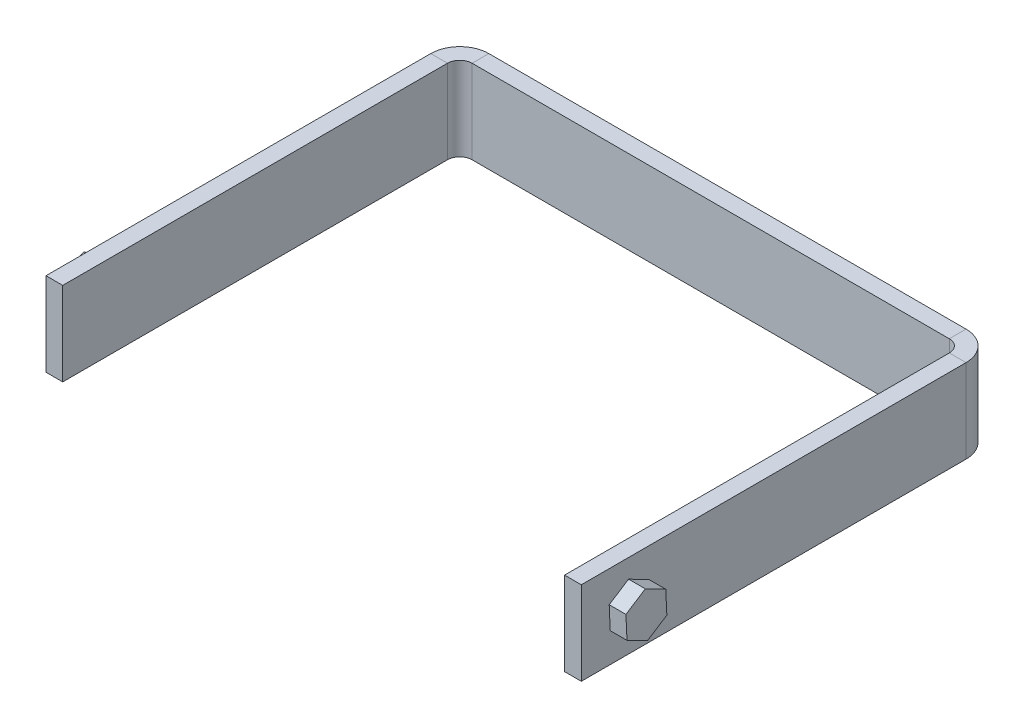
SolidWorks part; units mm, degrees
note: The reader was unsure of these and kept them because the rebuilt part matched: flange length of "Edge-Flange1".
ref_plane "Front Plane" through (0, 0, 0) normal (0, 0, 1) x (1, 0, 0)
ref_plane "Top Plane" through (0, 0, 0) normal (0, 1, 0) x (1, 0, 0)
ref_plane "Right Plane" through (0, 0, 0) normal (1, 0, 0) x (0, 0, -1)
sketch "Sketch1" plane through (0, 0, 0) normal (0, 0, 1) x (1, 0, 0)
  line L1 (-16, 2.5) -> (16, 2.5)
  line L2 (-16, 2.5) -> (-16, -2.5)
  line L3 (-16, -2.5) -> (16, -2.5)
  line L4 (16, 2.5) -> (16, -2.5)
  line L5 (-16, 2.5) -> (16, -2.5) construction
  line L6 (-16, -2.5) -> (16, 2.5) construction
  point P0 (0, 0)
  dimension "D1" = 32
  dimension "D2" = 5
base flange "Base-Flange1" sketch "Sketch1" thickness 1 reverse thickness direction no parameters "D1"=0.7366
edge flange "Edge-Flange1" sketch "Sketch10" flange profiles "Sketch10", "Sketch11" flange angle 90 flange length 24.7366 bend radius 0.7366 thickness 1 relief rectangular parameters "D6"=10, "D8"=0.2
sketch "Sketch10" plane through (-16, 0, 0) normal (-1, 0, 0) x (0, -1, 0)
  line L0 (-2.5, 0) -> (2.5, 0) construction
  line L1 (-2.5, 0) -> (2.5, 0)
  line L2 (-2.5, 0) -> (-2.5, 23.7366)
  line L3 (-2.5, 23.7366) -> (2.5, 23.7366)
  line L4 (2.5, 23.7366) -> (2.5, 0)
sketch "Sketch11" plane through (16, 0, 0) normal (1, 0, 0) x (0, 1, 0)
  line L0 (-2.5, 0) -> (2.5, 0) construction
  line L1 (-2.5, 0) -> (2.5, 0)
  line L2 (-2.5, 0) -> (-2.5, 23.7366)
  line L3 (-2.5, 23.7366) -> (2.5, 23.7366)
  line L4 (2.5, 23.7366) -> (2.5, 0)
bend "EdgeBend1" bend radius 0.7366 bend angle 90 parameters "D5"=1
bend "EdgeBend2" bend radius 0.7366 bend angle 90 parameters "D5"=2
sketch "Sketch12" plane through (16, 0, 0) normal (1, 0, 0) x (0, 0, -1)
  line L1 (-19.6229, -0.6329) -> (-19.6864, 0.7428)
  line L2 (-19.6864, 0.7428) -> (-20.9095, 1.3757)
  line L3 (-20.9095, 1.3757) -> (-22.0691, 0.6329)
  line L4 (-22.0691, 0.6329) -> (-22.0057, -0.7428)
  line L5 (-22.0057, -0.7428) -> (-20.7826, -1.3757)
  line L6 (-20.7826, -1.3757) -> (-19.6229, -0.6329)
  circle A0 centre (-20.846, 0) radius 1.1926 construction
extrude "Boss-Extrude1" add sketch "Sketch12" along normal blind 1
sketch "Sketch13" plane through (-16, 0, 0) normal (-1, 0, 0) x (0, 0, 1)
  line L1 (22.1414, -0.6499) -> (21.9623, 0.9602)
  line L2 (21.9623, 0.9602) -> (20.4784, 1.61)
  line L3 (20.4784, 1.61) -> (19.1736, 0.6499)
  line L4 (19.1736, 0.6499) -> (19.3528, -0.9602)
  line L5 (19.3528, -0.9602) -> (20.8367, -1.61)
  line L6 (20.8367, -1.61) -> (22.1414, -0.6499)
  circle A0 centre (20.6575, 0) radius 1.4029 construction
extrude "Boss-Extrude2" add sketch "Sketch13" along normal blind 1
sketch "Bend-Lines1" [suppressed] plane through (0, 0, 0) normal (0, 1, 0) x (1, 0, 0)
sketch "Bounding-Box1" [suppressed] plane through (0, 0, 0) normal (0, 1, 0) x (1, 0, 0)
sheet metal parameters "Sheet-Metal1" thickness 1 parameters "D1"=0.7366
flat pattern "Flat-Pattern1" [suppressed]
sketch "Bend-Lines2" plane through (0, 0, 0) normal (0, 1, 0) x (1, 0, 0)
sketch3d "Bounding-Box2" [suppressed]
  line L0 (12.5, -2.5, 0) -> (-12.5, -2.5, 0) construction
  line L1 (12.5, 2.5, 0) -> (-12.5, 2.5, 0) construction
  line L2 (12.5, -2.5, 0) -> (12.5, 2.5, 0) construction
  line L3 (-12.5, -2.5, 0) -> (-12.5, 2.5, 0) construction
sheet metal parameters "Sheet-Metal2" thickness 1 parameters "D1"=0.7366
flat pattern "Flat-Pattern1"
sketch "Bend-Lines2" plane through (0, 0, 0) normal (0, 0, 1) x (1, 0, 0)
  line L0 (15.2346, -2.5) -> (15.2346, 2.5) construction
  line L1 (-15.2346, 2.5) -> (-15.2346, -2.5) construction
  line L2 (15.2346, -2.5) -> (15.2346, 2.5) construction
  line L3 (-15.2346, 2.5) -> (-15.2346, -2.5) construction
sketch3d "Bounding-Box2" [suppressed]
  line L0 (-39.2058, -2.5, 0) -> (39.2058, -2.5, 0) construction
  line L1 (-39.2058, 2.5, 0) -> (39.2058, 2.5, 0) construction
  line L2 (-39.2058, -2.5, 0) -> (-39.2058, 2.5, 0) construction
  line L3 (39.2058, -2.5, 0) -> (39.2058, 2.5, 0) construction
bend of the flat pattern "Flatten-<EdgeBend1>1"
bend of the flat pattern "Flatten-<EdgeBend2>1"
sheet metal parameters "Sheet-Metal3" thickness 1 parameters "D1"=0.7366
flat pattern "Flat-Pattern1"
sketch "Bend-Lines2" plane through (0, 0, 0) normal (0, 0, 1) x (1, 0, 0)
  line L0 (15.2346, -2.5) -> (15.2346, 2.5) construction
  line L1 (-15.2346, 2.5) -> (-15.2346, -2.5) construction
  line L2 (15.2346, -2.5) -> (15.2346, 2.5) construction
  line L3 (-15.2346, 2.5) -> (-15.2346, -2.5) construction
sketch3d "Bounding-Box2" [suppressed]
  line L0 (-39.2058, -2.5, 0) -> (39.2058, -2.5, 0) construction
  line L1 (-39.2058, 2.5, 0) -> (39.2058, 2.5, 0) construction
  line L2 (-39.2058, -2.5, 0) -> (-39.2058, 2.5, 0) construction
  line L3 (39.2058, -2.5, 0) -> (39.2058, 2.5, 0) construction
bend of the flat pattern "Flatten-<EdgeBend1>1"
bend of the flat pattern "Flatten-<EdgeBend2>1"
sheet metal parameters "Sheet-Metal4" thickness 1 parameters "D1"=0.7366
flat pattern "Flat-Pattern1"
sketch "Bend-Lines2" plane through (0, 0, 0) normal (0, 0, 1) x (1, 0, 0)
  line L0 (15.2346, -2.5) -> (15.2346, 2.5) construction
  line L1 (-15.2346, 2.5) -> (-15.2346, -2.5) construction
  line L2 (15.2346, -2.5) -> (15.2346, 2.5) construction
  line L3 (-15.2346, 2.5) -> (-15.2346, -2.5) construction
sketch3d "Bounding-Box2" [suppressed]
  line L0 (-39.2058, -2.5, 0) -> (39.2058, -2.5, 0) construction
  line L1 (-39.2058, 2.5, 0) -> (39.2058, 2.5, 0) construction
  line L2 (-39.2058, -2.5, 0) -> (-39.2058, 2.5, 0) construction
  line L3 (39.2058, -2.5, 0) -> (39.2058, 2.5, 0) construction
bend of the flat pattern "Flatten-<EdgeBend1>1"
bend of the flat pattern "Flatten-<EdgeBend2>1"
